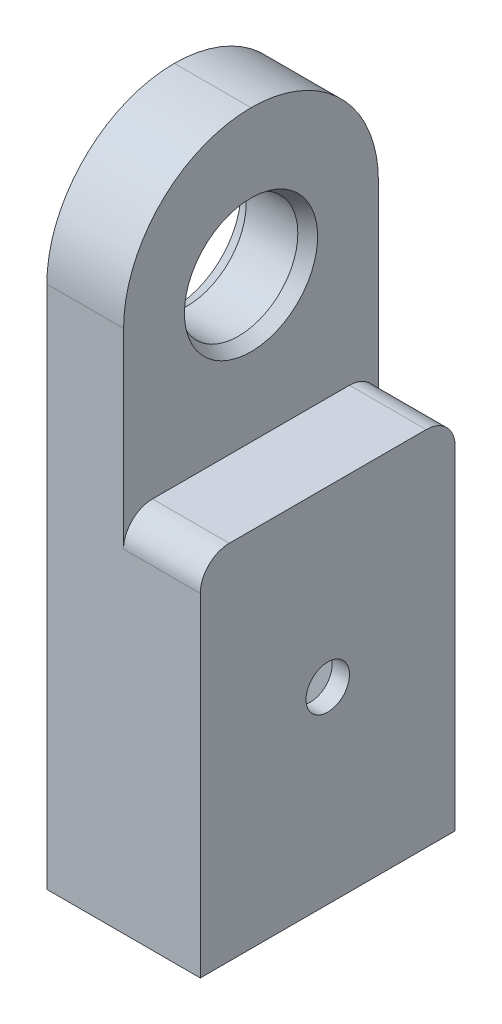
SolidWorks part; units mm, degrees
ref_plane "Front Plane" through (0, 0, 0) normal (0, 0, 1) x (1, 0, 0)
ref_plane "Top Plane" through (0, 0, 0) normal (0, 1, 0) x (1, 0, 0)
ref_plane "Right Plane" through (0, 0, 0) normal (1, 0, 0) x (0, 0, -1)
sketch "Sketch1" plane through (0, 0, 0) normal (0, 1, 0) x (1, 0, 0)
  line L1 (-5.3, -8.8) -> (5.3, -8.8)
  line L2 (-5.3, -8.8) -> (-5.3, 8.8)
  line L3 (-5.3, 8.8) -> (5.3, 8.8)
  line L4 (5.3, -8.8) -> (5.3, 8.8)
  line L5 (-5.3, -8.8) -> (5.3, 8.8) construction
  line L6 (-5.3, 8.8) -> (5.3, -8.8) construction
  point P0 (0, 0)
  dimension "D1" = 10.6
  dimension "D2" = 17.6
extrude "Boss-Extrude1" add sketch "Sketch1" along normal blind 25
sketch "Sketch2" plane through (0, 0, 0) normal (0, -1, 0) x (1, 0, 0)
  line L1 (-4.1, -7.6) -> (4.1, -7.6)
  line L2 (-4.1, -7.6) -> (-4.1, 7.6)
  line L3 (-4.1, 7.6) -> (4.1, 7.6)
  line L4 (4.1, -7.6) -> (4.1, 7.6)
  line L5 (-4.1, -7.6) -> (4.1, 7.6) construction
  line L6 (-4.1, 7.6) -> (4.1, -7.6) construction
  point P0 (0, 0)
  dimension "D1" = 8.2
  dimension "D2" = 15.2
extrude "Cut-Extrude1" cut sketch "Sketch2" against normal blind 23
sketch "Sketch4" plane through (0, 25, 0) normal (0, 1, 0) x (1, 0, 0)
  line L5 (-5.3, -8.8) -> (0, -8.8)
  line L6 (-5.3, -8.8) -> (-5.3, 8.8)
  line L7 (-5.3, 8.8) -> (0, 8.8)
  line L8 (0, -8.8) -> (0, 8.8)
  line L9 (-5.3, -8.8) -> (0, 8.8) construction
  line L10 (-5.3, 8.8) -> (0, -8.8) construction
  line L11 (-5.83, 0) -> (5.83, 0) construction
  line L12 (0, -9.68) -> (0, 9.68) construction
  point P0 (-2.65, 0)
  dimension "D1" = 5.3
  dimension "D2" = 17.6
extrude "Boss-Extrude2" add sketch "Sketch4" along normal blind 20
sketch "Sketch5" plane through (0, 0, 0) normal (1, 0, 0) x (0, 0, -1)
  line L0 (-8.8, 45) -> (8.8, 45) construction
  circle A0 centre (0, 35) radius 4.1
  dimension "D2" = 8.2
  dimension "D1" = 10
extrude "Cut-Extrude2" cut sketch "Sketch5" against normal up to next
fillet "Fillet1" radius 8.8 2 edges at (-2.65, 45, -8.8) (-2.65, 45, 8.8)
fillet "Fillet2" radius 2 2 edges at (2.65, 25, 8.8) (2.65, 25, -8.8)
sketch "Sketch6" plane through (5.3, 0, 0) normal (1, 0, 0) x (0, 0, -1)
  line L0 (-7.6, 23) -> (7.6, 23) construction
  circle A0 centre (0, 13) radius 1.5
  dimension "D2" = 3
  dimension "D1" = 10
extrude "Cut-Extrude3" cut sketch "Sketch6" against normal through all
chamfer "Chamfer1" distance 0.5 angle 60 2 edges at (-5.3, 35, -4.1) (0, 35, -4.1) first distance on face at (-5.3, 13, -1.5) first distance on face at (0, 35, -4.1)
